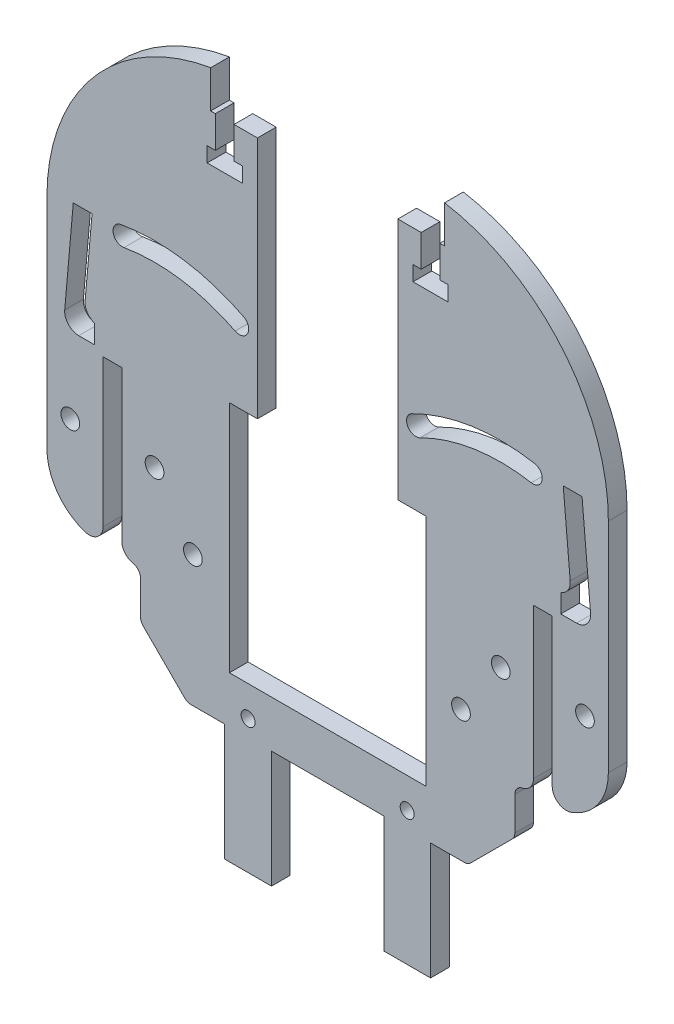
SolidWorks part; units mm, degrees
material "Acrylic (Medium-high impact)"
ref_plane "Front Plane" through (0, 0, 0) normal (0, 0, 1) x (1, 0, 0)
ref_plane "Top Plane" through (0, 0, 0) normal (0, 1, 0) x (1, 0, 0)
ref_plane "Right Plane" through (0, 0, 0) normal (1, 0, 0) x (0, 0, -1)
sketch "Sketch1" plane through (0, 0, 0) normal (0, 0, 1) x (1, 0, 0)
  line L0 (0, 0) -> (0, -98.0129) construction
  line L1 (-40, 60) -> (-25, 60)
  line L2 (-40, 60) -> (-40, -60)
  line L3 (-40, -60) -> (-22, -60)
  line L4 (40, 60) -> (40, -60)
  line L5 (-40, 60) -> (40, -60) construction
  line L6 (-40, -60) -> (40, 60) construction
  line L7 (21, 0) -> (21, -50)
  line L8 (0, 0) -> (0, 75) construction
  line L9 (-21, -50) -> (21, -50)
  line L10 (15, 0) -> (15, 52)
  line L11 (-15, 0) -> (-15, 52)
  line L12 (-15, 0) -> (-15, 85.1588) construction
  line L13 (0, 0) -> (0, 85.1588) construction
  line L14 (15, 0) -> (15, 85.1588) construction
  line L15 (25, 60) -> (40, 60)
  line L16 (-15, 0) -> (-21, 0)
  line L17 (15, 0) -> (21, 0)
  line L18 (-21, 0) -> (-21, -50)
  line L19 (-12, -60) -> (12, -60)
  line L21 (-15, 52) -> (-25, 52)
  line L22 (-25, 60) -> (-25, 52)
  line L23 (22, -60) -> (22, -85)
  line L24 (22, -85) -> (12, -85)
  line L25 (15, 52) -> (25, 52)
  line L26 (25, 60) -> (25, 52)
  line L27 (12, -60) -> (12, -85)
  line L28 (22, -60) -> (40, -60)
  line L29 (-12, -60) -> (-12, -85)
  line L30 (-12, -85) -> (-22, -85)
  line L31 (-22, -60) -> (-22, -85)
  point P0 (0, 0)
  dimension "D1" = 120
  dimension "D2" = 80
  dimension "D3" = 50
  dimension "D4" = 8
  dimension "D5" = 110
  dimension "D8" = 8
  dimension "D9" = 50
  dimension "D10" = 25
  dimension "D11" = 42
  dimension "D12" = 25
  dimension "D13" = 10
  dimension "D14" = 24
  dimension "D15" = 12
  dimension "D6" = 15
  dimension "D7" = 15
extrude "Boss-Extrude1" add sketch "Sketch1" along normal blind 4
sketch "Sketch2" plane through (0, 0, 0) normal (0, 0, -1) x (-1, 0, 0)
  line L1 (-21, 0) -> (-21, -50) construction
  line L2 (40, -60) -> (22, -60) construction
  line L3 (28.8, -32) -> (28.8, 8.3751) construction
  line L4 (22, -85) -> (12, -85) construction
  line L5 (-12, -85) -> (-22, -85) construction
  line L6 (21, -50) -> (21, 0) construction
  line L7 (-28.5, -12) -> (-28.5, -69.2337) construction
  line L9 (40, -60) -> (22, -60) construction
  circle A0 centre (-28.5, -32) radius 2
  circle A1 centre (17, -56.5) radius 1.5
  circle A2 centre (28.8, -32) radius 2
  circle A3 centre (-17, -56.5) radius 1.5
  point P21 (17, -85)
  point P24 (-17, -85)
  dimension "D1" = 4
  dimension "D6" = 3
  dimension "D2" = 7.5
  dimension "D3" = 57.3
  dimension "D4" = 28
  dimension "D5" = 28
  dimension "D7" = 3.5
extrude "Cut-Extrude1" cut sketch "Sketch2" against normal through all
ref_plane "Plane1" through (0, 0, -2) normal (0, 0, 1) x (1, 0, 0)
sketch "Sketch4" plane through (0, 0, 4) normal (0, 0, 1) x (1, 0, 0)
  line L1 (-40, 60) -> (-60, 60)
  line L2 (-40, 60) -> (-40, -40)
  line L3 (-40, -40) -> (-60, -40)
  line L4 (-60, 60) -> (-60, -40)
  line L5 (40, 60) -> (60, 60)
  line L6 (40, 60) -> (40, -40)
  line L7 (40, -40) -> (60, -40)
  line L8 (60, 60) -> (60, -40)
  dimension "D1" = 20
  dimension "D2" = 20
  dimension "D3" = 100
  dimension "D4" = 100
extrude "Boss-Extrude2" add sketch "Sketch4" against normal blind 4
fillet "Fillet3" radius 42 2 edges at (60, 60, 2) (-60, 60, 2)
fillet "Fillet4" radius 12 2 edges at (60, -40, 2) (-60, -40, 2)
sketch "Sketch7" plane through (0, 0, 0) normal (0, 0, 1) x (1, 0, 0)
  line L1 (-60, 18.5874) -> (-60, -28) construction
  line L2 (60, -28) -> (60, 18.5874) construction
  line L3 (22, -60) -> (40, -60) construction
  line L4 (-40, -60) -> (-22, -60) construction
  circle A0 centre (-55, -20) radius 2
  circle A1 centre (55, -20) radius 2
  circle A2 centre (-37, -20) radius 2
  circle A3 centre (37, -20) radius 2
  point P10 (-60, -4.7063)
  dimension "D3" = 5
  dimension "D4" = 5
  dimension "D5" = 4
  dimension "D6" = 4
  dimension "D7" = 4
  dimension "D1" = 40
  dimension "D2" = 40
  dimension "D8" = 18
  dimension "D9" = 18
extrude "Cut-Extrude3" cut sketch "Sketch7" along normal through all
chamfer "Chamfer1" distance 10 angle 45 2 edges at (-40, -60, 2) (40, -60, 2)
fillet "Fillet8" radius 2 6 edges at (-30, -60, 2) (-40, -50, 2) (30, -60, 2) (40, -50, 2)
sketch "Sketch8" plane through (0, 0, 0) normal (0, 0, -1) x (-1, 0, 0)
  line L0 (0, 0) -> (0, 75) construction
  line L1 (0, 0) -> (0, 75)
  circle A0 centre (-37, -20) radius 40 construction
  arc A1 (-18.8713, 15.656) -> (-43.8713, 19.4054) centre (-37, -20) ccw construction
  arc A2 (-17.9648, 17.4388) -> (-44.2148, 21.3757) centre (-37, -20) ccw
  arc A3 (-19.7777, 13.8732) -> (-43.5277, 17.4351) centre (-37, -20) ccw
  arc A4 (-19.7777, 13.8732) -> (-17.9648, 17.4388) centre (-18.8713, 15.656) ccw
  arc A5 (-44.2148, 21.3757) -> (-43.5277, 17.4351) centre (-43.8713, 19.4054) ccw
  arc A6 (18.8713, 15.656) -> (43.8713, 19.4054) centre (37, -20) cw construction
  arc A7 (17.9648, 17.4388) -> (44.2148, 21.3757) centre (37, -20) cw
  arc A8 (19.7777, 13.8732) -> (43.5277, 17.4351) centre (37, -20) cw
  arc A9 (19.7777, 13.8732) -> (17.9648, 17.4388) centre (18.8713, 15.656) cw
  arc A10 (44.2148, 21.3757) -> (43.5277, 17.4351) centre (43.8713, 19.4054) cw
  point P5 (-31.0673, 19.5576)
  point P15 (31.0673, 19.5576)
  dimension "D1" = 80
  dimension "D2" = 2
  dimension "D3" = 25
extrude "Cut-Extrude4" cut sketch "Sketch8" against normal through all contours A7 A10 A8 A9 | A2 A5 A3 A4
sketch "Sketch9" plane through (0, 0, 4) normal (0, 0, 1) x (1, 0, 0)
  line L0 (-15, 52) -> (-25, 52) construction
  line L1 (-24, 52) -> (-20, 52)
  line L2 (-24, 52) -> (-24, 45.2)
  line L3 (-22, 40.3094) -> (-22, 51.6327) construction
  line L4 (-20, 52) -> (-20, 45.2)
  line L5 (-25, 52) -> (-25, 60) construction
  line L6 (-20, 45.2) -> (-18.25, 45.2)
  line L7 (-25.75, 45.2) -> (-24, 45.2)
  line L8 (-25.75, 45.2) -> (-25.75, 42)
  line L9 (-25.75, 42) -> (-18.25, 42)
  line L10 (-18.25, 45.2) -> (-18.25, 42)
  dimension "D1" = 3
  dimension "D2" = 2
  dimension "D3" = 2
  dimension "D4" = 7.5
  dimension "D5" = 3.2
  dimension "D6" = 10
  dimension "D7" = 3.75
extrude "Cut-Extrude5" cut sketch "Sketch9" against normal through all
mirror "Mirror1" about plane through (0, 0, 0) normal (1, 0, 0) of "Cut-Extrude5"
sketch "Sketch10" plane through (0, 0, 4) normal (0, 0, 1) x (1, 0, 0)
  line L0 (42, -40) -> (48, -40) construction
  line L1 (48, -40) -> (48, -3.7032)
  line L2 (48, -3.7032) -> (56.4853, -3.7032)
  line L3 (56.4853, -3.7032) -> (53.8429, 26.2968)
  line L5 (44, -40) -> (44, 0.2968)
  line L6 (44, 0.2968) -> (52.1175, 0.2968)
  line L7 (52.1175, 0.2968) -> (49.8275, 26.2968)
  line L10 (49.8275, 26.2968) -> (53.8429, 26.2968)
  line L11 (49.8275, 0.2968) -> (49.8275, -3.7032)
  line L12 (44, -5) -> (48, -5)
  line L14 (50.3559, 20.2968) -> (54.3714, 20.2968)
  line L15 (44, -40) -> (48, -40)
  line L16 (42, -40) -> (48, -40)
  dimension "D2" = 66.2968
  dimension "D3" = 35
  dimension "D4" = 24
  dimension "D5" = 2
  dimension "D7" = 4
  dimension "D10" = 6
  dimension "D12" = 4
  dimension "D13" = 4
  dimension "D14" = 8.1175
  dimension "D15" = 8.4853
extrude "Cut-Extrude6" cut sketch "Sketch10" against normal through all contours L5 L15 L1 L12 | L14 L7 L6 L11 L2 L3 region at (46, -22.5, 4) region at (53.2017, 7.3639, 4)
mirror "Mirror2" about plane through (0, 0, 0) normal (1, 0, 0) of "Cut-Extrude6"
fillet "Fillet9" radius 3 8 edges at (56.4853, -3.7032, 2) (52.1175, 0.2968, 2) (48, -40, 2) (44, -40, 2) (-44, -40, 2) (-48, -40, 2) (-52.1175, 0.2968, 2) (-56.4853, -3.7032, 2)
